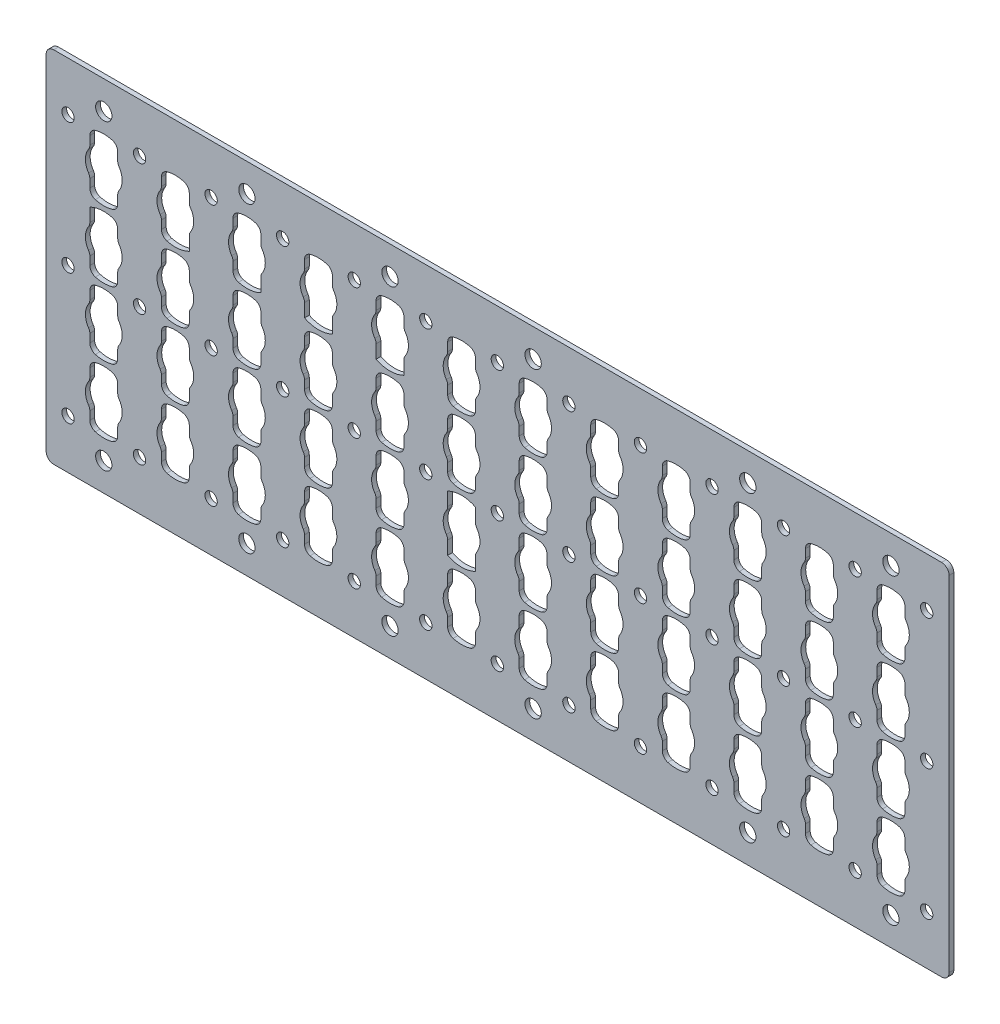
SolidWorks part; units mm, degrees
material "E-Glass Fiber"
ref_plane "X-Y Datum" through (0, 0, 0) normal (0, 0, 1) x (1, 0, 0)
ref_plane "X-Z Datum" through (0, 0, 0) normal (0, 1, 0) x (1, 0, 0)
ref_plane "Y-Z Datum" through (0, 0, 0) normal (1, 0, 0) x (0, 0, -1)
sketch "Sketch1" plane through (0, 0, 0) normal (0, 0, 1) x (1, 0, 0)
  line L1 (-10.2406, 8) -> (78.318, 8)
  line L2 (-10.2406, 8) -> (-10.2406, 16.1972)
  line L7 (-10.2406, 16.1972) -> (78.318, 16.1972)
  line L8 (78.318, 8) -> (78.318, 16.1972)
  line L12 (84.583, 16.1972) -> (87.883, 16.1972) construction
  line L17 (84.583, 4.7) -> (87.883, 4.7) construction
  line L20 (78.318, 0) -> (82.128, 0) construction
  circle A0 centre (0, 0) radius 10.5
  circle A24 centre (0, 0) radius 8 construction
  circle A25 centre (0, 0) radius 4.7 construction
  circle A46 centre (-3.5188, 13.3573) radius 2.5146 construction
  circle A47 centre (-3.5188, 13.3573) radius 1.1913 construction
  circle A78 centre (22.606, 0) radius 10.5
  circle A79 centre (22.606, 0) radius 8 construction
  circle A80 centre (22.606, 0) radius 4.7 construction
  circle A81 centre (45.212, 0) radius 10.5
  circle A82 centre (45.212, 0) radius 8 construction
  circle A83 centre (45.212, 0) radius 4.7 construction
  circle A84 centre (67.818, 0) radius 10.5
  circle A85 centre (67.818, 0) radius 8 construction
  circle A86 centre (67.818, 0) radius 4.7 construction
  circle A87 centre (0, 24.13) radius 10.5
  circle A88 centre (0, 24.13) radius 8 construction
  circle A89 centre (0, 24.13) radius 4.7 construction
  circle A90 centre (22.606, 24.13) radius 10.5
  circle A91 centre (22.606, 24.13) radius 8 construction
  circle A92 centre (22.606, 24.13) radius 4.7 construction
  circle A93 centre (45.212, 24.13) radius 10.5
  circle A94 centre (45.212, 24.13) radius 8 construction
  circle A95 centre (45.212, 24.13) radius 4.7 construction
  circle A96 centre (67.818, 24.13) radius 10.5
  circle A97 centre (67.818, 24.13) radius 8 construction
  circle A98 centre (67.818, 24.13) radius 4.7 construction
  circle A99 centre (0, 48.26) radius 10.5
  circle A100 centre (0, 48.26) radius 8 construction
  circle A101 centre (0, 48.26) radius 4.7 construction
  circle A102 centre (22.606, 48.26) radius 10.5
  circle A103 centre (22.606, 48.26) radius 8 construction
  circle A104 centre (22.606, 48.26) radius 4.7 construction
  circle A105 centre (45.212, 48.26) radius 10.5
  circle A106 centre (45.212, 48.26) radius 8 construction
  circle A107 centre (45.212, 48.26) radius 4.7 construction
  circle A108 centre (67.818, 48.26) radius 10.5
  circle A109 centre (67.818, 48.26) radius 8 construction
  circle A110 centre (67.818, 48.26) radius 4.7 construction
  circle A111 centre (0, 72.39) radius 10.5
  circle A112 centre (0, 72.39) radius 8 construction
  circle A113 centre (0, 72.39) radius 4.7 construction
  circle A114 centre (22.606, 72.39) radius 10.5
  circle A115 centre (22.606, 72.39) radius 8 construction
  circle A116 centre (22.606, 72.39) radius 4.7 construction
  circle A117 centre (45.212, 72.39) radius 10.5
  circle A118 centre (45.212, 72.39) radius 8 construction
  circle A119 centre (45.212, 72.39) radius 4.7 construction
  circle A120 centre (67.818, 72.39) radius 10.5
  circle A121 centre (67.818, 72.39) radius 8 construction
  circle A122 centre (67.818, 72.39) radius 4.7 construction
  circle A123 centre (0, 96.52) radius 10.5
  circle A124 centre (0, 96.52) radius 8 construction
  circle A125 centre (0, 96.52) radius 4.7 construction
  circle A126 centre (22.606, 96.52) radius 10.5
  circle A127 centre (22.606, 96.52) radius 8 construction
  circle A128 centre (22.606, 96.52) radius 4.7 construction
  circle A129 centre (45.212, 96.52) radius 10.5
  circle A130 centre (45.212, 96.52) radius 8 construction
  circle A131 centre (45.212, 96.52) radius 4.7 construction
  circle A132 centre (67.818, 96.52) radius 10.5
  circle A133 centre (67.818, 96.52) radius 8 construction
  circle A134 centre (67.818, 96.52) radius 4.7 construction
  circle A135 centre (0, 120.65) radius 10.5
  circle A136 centre (0, 120.65) radius 8 construction
  circle A137 centre (0, 120.65) radius 4.7 construction
  circle A138 centre (22.606, 120.65) radius 10.5
  circle A139 centre (22.606, 120.65) radius 8 construction
  circle A140 centre (22.606, 120.65) radius 4.7 construction
  circle A141 centre (45.212, 120.65) radius 10.5
  circle A142 centre (45.212, 120.65) radius 8 construction
  circle A143 centre (45.212, 120.65) radius 4.7 construction
  circle A144 centre (67.818, 120.65) radius 10.5
  circle A145 centre (67.818, 120.65) radius 8 construction
  circle A146 centre (67.818, 120.65) radius 4.7 construction
  dimension "D1" = 4
  dimension "D9" = 9.4
  dimension "D4" = 2.5
  dimension "D2" = 6
sketch "Sketch2" plane through (0, 0, 0) normal (0, 0, 1) x (1, 0, 0)
  line L0 (28.8471, 78.318) -> (28.8471, -10.5) construction
  line L5 (4.7, 78.318) -> (19.43, 78.318) construction
  line L6 (4.7, 78.318) -> (4.7, -10.5) construction
  line L7 (4.7, -10.5) -> (19.43, -10.5) construction
  line L8 (19.43, 78.318) -> (19.43, -10.5) construction
  line L9 (28.8471, 78.318) -> (43.5771, 78.318) construction
  line L10 (43.5771, 78.318) -> (43.5771, -10.5) construction
  line L11 (28.8471, -10.5) -> (43.5771, -10.5) construction
  line L12 (52.9942, 78.318) -> (52.9942, -10.5) construction
  line L13 (52.9942, 78.318) -> (67.7242, 78.318) construction
  line L14 (67.7242, 78.318) -> (67.7242, -10.5) construction
  line L15 (52.9942, -10.5) -> (67.7242, -10.5) construction
  line L16 (77.1413, 78.318) -> (77.1413, -10.5) construction
  line L17 (77.1413, 78.318) -> (91.8713, 78.318) construction
  line L18 (91.8713, 78.318) -> (91.8713, -10.5) construction
  line L19 (77.1413, -10.5) -> (91.8713, -10.5) construction
  line L20 (101.2884, 78.318) -> (101.2884, -10.5) construction
  line L21 (101.2884, 78.318) -> (116.0184, 78.318) construction
  line L22 (116.0184, 78.318) -> (116.0184, -10.5) construction
  line L23 (101.2884, -10.5) -> (116.0184, -10.5) construction
  line L24 (125.4355, 78.318) -> (125.4355, -10.5) construction
  line L25 (125.4355, 78.318) -> (140.1655, 78.318) construction
  line L26 (140.1655, 78.318) -> (140.1655, -10.5) construction
  line L27 (125.4355, -10.5) -> (140.1655, -10.5) construction
  line L28 (149.5826, 78.318) -> (149.5826, -10.5) construction
  line L29 (149.5826, 78.318) -> (164.3126, 78.318) construction
  line L30 (164.3126, 78.318) -> (164.3126, -10.5) construction
  line L31 (149.5826, -10.5) -> (164.3126, -10.5) construction
  line L32 (173.7297, 78.318) -> (173.7297, -10.5) construction
  line L33 (173.7297, 78.318) -> (188.4597, 78.318) construction
  line L34 (188.4597, 78.318) -> (188.4597, -10.5) construction
  line L35 (173.7297, -10.5) -> (188.4597, -10.5) construction
  line L36 (197.8768, 78.318) -> (197.8768, -10.5) construction
  line L37 (197.8768, 78.318) -> (212.6068, 78.318) construction
  line L38 (212.6068, 78.318) -> (212.6068, -10.5) construction
  line L39 (197.8768, -10.5) -> (212.6068, -10.5) construction
  line L40 (222.0239, 78.318) -> (222.0239, -10.5) construction
  line L41 (222.0239, 78.318) -> (236.7539, 78.318) construction
  line L42 (236.7539, 78.318) -> (236.7539, -10.5) construction
  line L43 (222.0239, -10.5) -> (236.7539, -10.5) construction
  line L44 (246.171, 78.318) -> (246.171, -10.5) construction
  line L45 (246.171, 78.318) -> (260.901, 78.318) construction
  line L46 (260.901, 78.318) -> (260.901, -10.5) construction
  line L47 (246.171, -10.5) -> (260.901, -10.5) construction
  line L48 (270.3181, 78.318) -> (270.3181, -10.5) construction
  line L49 (270.3181, 78.318) -> (285.0481, 78.318) construction
  line L50 (285.0481, 78.318) -> (285.0481, -10.5) construction
  line L51 (270.3181, -10.5) -> (285.0481, -10.5) construction
  line L52 (-19.43, 78.318) -> (-19.43, -10.5) construction
  line L53 (-19.43, 78.318) -> (-4.7, 78.318) construction
  line L54 (-4.7, 78.318) -> (-4.7, -10.5) construction
  line L55 (-19.43, -10.5) -> (-4.7, -10.5) construction
  line L56 (0, 78.3179) -> (0, 91.526) construction
  line L57 (0, -10.4999) -> (0, -23.708) construction
  line L58 (-27.6439, 33.909) -> (301.0934, 33.909) construction
  line L59 (-19.43, 91.526) -> (285.0481, 91.526) construction
  line L60 (-19.43, 91.526) -> (-19.43, -23.708)
  line L61 (-19.43, -23.708) -> (285.0481, -23.708) construction
  line L62 (285.0481, 91.526) -> (285.0481, -23.708)
  line L63 (-19.43, 91.526) -> (-19.43, 94.447)
  line L64 (-19.43, 94.447) -> (285.0481, 94.447)
  line L65 (285.0481, 94.447) -> (285.0481, 91.526)
  line L66 (-19.43, -23.708) -> (-19.43, -26.629)
  line L67 (-19.43, -26.629) -> (285.0481, -26.629)
  line L68 (285.0481, -26.629) -> (285.0481, -23.708)
  circle A0 centre (0, 0) radius 10.4999
  circle A8 centre (0, 0) radius 4.7 construction
  circle A10 centre (24.13, 0) radius 10.4999
  circle A11 centre (48.26, 0) radius 10.4999
  circle A12 centre (72.39, 0) radius 10.4999
  circle A13 centre (24.13, 22.606) radius 10.4999
  circle A14 centre (48.26, 22.606) radius 10.4999
  circle A15 centre (72.39, 22.606) radius 10.4999
  circle A16 centre (24.13, 45.212) radius 10.4999
  circle A17 centre (48.26, 45.212) radius 10.4999
  circle A18 centre (72.39, 45.212) radius 10.4999
  circle A19 centre (24.13, 67.818) radius 10.4999
  circle A20 centre (48.26, 67.818) radius 10.4999
  circle A21 centre (72.39, 67.818) radius 10.4999
  circle A28 centre (0, 22.606) radius 10.4999
  circle A29 centre (0, 45.212) radius 10.4999
  circle A30 centre (0, 67.818) radius 10.4999
  circle A33 centre (0, 0) radius 8 construction
  circle A34 centre (96.52, 0) radius 10.4999
  circle A35 centre (120.65, 0) radius 10.4999
  circle A36 centre (144.78, 0) radius 10.4999
  circle A37 centre (168.91, 0) radius 10.4999
  circle A38 centre (193.04, 0) radius 10.4999
  circle A39 centre (217.17, 0) radius 10.4999
  circle A40 centre (241.3, 0) radius 10.4999
  circle A41 centre (265.43, 0) radius 10.4999
  circle A42 centre (96.52, 22.606) radius 10.4999
  circle A43 centre (120.65, 22.606) radius 10.4999
  circle A44 centre (144.78, 22.606) radius 10.4999
  circle A45 centre (168.91, 22.606) radius 10.4999
  circle A46 centre (193.04, 22.606) radius 10.4999
  circle A47 centre (217.17, 22.606) radius 10.4999
  circle A48 centre (241.3, 22.606) radius 10.4999
  circle A49 centre (265.43, 22.606) radius 10.4999
  circle A50 centre (96.52, 45.212) radius 10.4999
  circle A51 centre (120.65, 45.212) radius 10.4999
  circle A52 centre (144.78, 45.212) radius 10.4999
  circle A53 centre (168.91, 45.212) radius 10.4999
  circle A54 centre (193.04, 45.212) radius 10.4999
  circle A55 centre (217.17, 45.212) radius 10.4999
  circle A56 centre (241.3, 45.212) radius 10.4999
  circle A57 centre (265.43, 45.212) radius 10.4999
  circle A58 centre (96.52, 67.818) radius 10.4999
  circle A59 centre (120.65, 67.818) radius 10.4999
  circle A60 centre (144.78, 67.818) radius 10.4999
  circle A61 centre (168.91, 67.818) radius 10.4999
  circle A62 centre (193.04, 67.818) radius 10.4999
  circle A63 centre (217.17, 67.818) radius 10.4999
  circle A64 centre (241.3, 67.818) radius 10.4999
  circle A65 centre (265.43, 67.818) radius 10.4999
  circle A82 centre (24.13, 0) radius 8 construction
  circle A83 centre (24.13, 0) radius 4.7 construction
  circle A84 centre (48.26, 0) radius 8 construction
  circle A85 centre (48.26, 0) radius 4.7 construction
  circle A86 centre (72.39, 0) radius 8 construction
  circle A87 centre (72.39, 0) radius 4.7 construction
  circle A88 centre (96.52, 0) radius 8 construction
  circle A89 centre (96.52, 0) radius 4.7 construction
  circle A90 centre (120.65, 0) radius 8 construction
  circle A91 centre (120.65, 0) radius 4.7 construction
  circle A92 centre (144.78, 0) radius 8 construction
  circle A93 centre (144.78, 0) radius 4.7 construction
  circle A94 centre (168.91, 0) radius 8 construction
  circle A95 centre (168.91, 0) radius 4.7 construction
  circle A96 centre (193.04, 0) radius 8 construction
  circle A97 centre (193.04, 0) radius 4.7 construction
  circle A98 centre (217.17, 0) radius 8 construction
  circle A99 centre (217.17, 0) radius 4.7 construction
  circle A100 centre (241.3, 0) radius 8 construction
  circle A101 centre (241.3, 0) radius 4.7 construction
  circle A102 centre (265.43, 0) radius 8 construction
  circle A103 centre (265.43, 0) radius 4.7 construction
  circle A104 centre (24.13, 22.606) radius 8 construction
  circle A105 centre (24.13, 22.606) radius 4.7 construction
  circle A106 centre (48.26, 22.606) radius 8 construction
  circle A107 centre (48.26, 22.606) radius 4.7 construction
  circle A108 centre (72.39, 22.606) radius 8 construction
  circle A109 centre (72.39, 22.606) radius 4.7 construction
  circle A110 centre (96.52, 22.606) radius 8 construction
  circle A111 centre (96.52, 22.606) radius 4.7 construction
  circle A112 centre (120.65, 22.606) radius 8 construction
  circle A113 centre (120.65, 22.606) radius 4.7 construction
  circle A114 centre (144.78, 22.606) radius 8 construction
  circle A115 centre (144.78, 22.606) radius 4.7 construction
  circle A116 centre (168.91, 22.606) radius 8 construction
  circle A117 centre (168.91, 22.606) radius 4.7 construction
  circle A118 centre (193.04, 22.606) radius 8 construction
  circle A119 centre (193.04, 22.606) radius 4.7 construction
  circle A120 centre (217.17, 22.606) radius 8 construction
  circle A121 centre (217.17, 22.606) radius 4.7 construction
  circle A122 centre (241.3, 22.606) radius 8 construction
  circle A123 centre (241.3, 22.606) radius 4.7 construction
  circle A124 centre (265.43, 22.606) radius 8 construction
  circle A125 centre (265.43, 22.606) radius 4.7 construction
  circle A126 centre (24.13, 45.212) radius 8 construction
  circle A127 centre (24.13, 45.212) radius 4.7 construction
  circle A128 centre (48.26, 45.212) radius 8 construction
  circle A129 centre (48.26, 45.212) radius 4.7 construction
  circle A130 centre (72.39, 45.212) radius 8 construction
  circle A131 centre (72.39, 45.212) radius 4.7 construction
  circle A132 centre (96.52, 45.212) radius 8 construction
  circle A133 centre (96.52, 45.212) radius 4.7 construction
  circle A134 centre (120.65, 45.212) radius 8 construction
  circle A135 centre (120.65, 45.212) radius 4.7 construction
  circle A136 centre (144.78, 45.212) radius 8 construction
  circle A137 centre (144.78, 45.212) radius 4.7 construction
  circle A138 centre (168.91, 45.212) radius 8 construction
  circle A139 centre (168.91, 45.212) radius 4.7 construction
  circle A140 centre (193.04, 45.212) radius 8 construction
  circle A141 centre (193.04, 45.212) radius 4.7 construction
  circle A142 centre (217.17, 45.212) radius 8 construction
  circle A143 centre (217.17, 45.212) radius 4.7 construction
  circle A144 centre (241.3, 45.212) radius 8 construction
  circle A145 centre (241.3, 45.212) radius 4.7 construction
  circle A146 centre (265.43, 45.212) radius 8 construction
  circle A147 centre (265.43, 45.212) radius 4.7 construction
  circle A148 centre (24.13, 67.818) radius 8 construction
  circle A149 centre (24.13, 67.818) radius 4.7 construction
  circle A150 centre (48.26, 67.818) radius 8 construction
  circle A151 centre (48.26, 67.818) radius 4.7 construction
  circle A152 centre (72.39, 67.818) radius 8 construction
  circle A153 centre (72.39, 67.818) radius 4.7 construction
  circle A154 centre (96.52, 67.818) radius 8 construction
  circle A155 centre (96.52, 67.818) radius 4.7 construction
  circle A156 centre (120.65, 67.818) radius 8 construction
  circle A157 centre (120.65, 67.818) radius 4.7 construction
  circle A158 centre (144.78, 67.818) radius 8 construction
  circle A159 centre (144.78, 67.818) radius 4.7 construction
  circle A160 centre (168.91, 67.818) radius 8 construction
  circle A161 centre (168.91, 67.818) radius 4.7 construction
  circle A162 centre (193.04, 67.818) radius 8 construction
  circle A163 centre (193.04, 67.818) radius 4.7 construction
  circle A164 centre (217.17, 67.818) radius 8 construction
  circle A165 centre (217.17, 67.818) radius 4.7 construction
  circle A166 centre (241.3, 67.818) radius 8 construction
  circle A167 centre (241.3, 67.818) radius 4.7 construction
  circle A168 centre (265.43, 67.818) radius 8 construction
  circle A169 centre (265.43, 67.818) radius 4.7 construction
  circle A170 centre (0, 22.606) radius 8 construction
  circle A171 centre (0, 22.606) radius 4.7 construction
  circle A172 centre (0, 45.212) radius 8 construction
  circle A173 centre (0, 45.212) radius 4.7 construction
  circle A174 centre (0, 67.818) radius 8 construction
  circle A175 centre (0, 67.818) radius 4.7 construction
  circle A178 centre (0, 84.922) radius 2.752
  circle A181 centre (48.26, 84.922) radius 2.752
  circle A183 centre (96.52, 84.922) radius 2.752
  circle A185 centre (144.78, 84.922) radius 2.752
  circle A188 centre (217.17, 84.922) radius 2.752
  circle A190 centre (265.43, 84.922) radius 2.752
  circle A191 centre (24.13, 84.922) radius 2.752 [skipped]
  circle A192 centre (72.39, 84.922) radius 2.752 [skipped]
  circle A193 centre (120.65, 84.922) radius 2.752 [skipped]
  circle A194 centre (193.04, 84.922) radius 2.752 [skipped]
  circle A195 centre (241.3, 84.922) radius 2.752 [skipped]
  circle A196 centre (168.91, 84.922) radius 2.752 [skipped]
  circle A197 centre (265.43, -17.104) radius 2.752
  circle A198 centre (217.17, -17.104) radius 2.752
  circle A199 centre (144.78, -17.104) radius 2.752
  circle A200 centre (96.52, -17.104) radius 2.752
  circle A201 centre (48.26, -17.104) radius 2.752
  circle A202 centre (0, -17.104) radius 2.752
  dimension "D1" = 12
  dimension "D3" = 12
  dimension "D5" = 12
  dimension "D2" = 4
  dimension "D4" = 2
extrude "Boss-Extrude1" add sketch "Sketch2" along normal blind 1.6
sketch "Sketch3" plane through (0, 0, 1.6) normal (0, 0, 1) x (1, 0, 0)
  line L0 (10.4999, 67.818) -> (13.6301, 67.818) construction
  line L1 (4.7, 78.318) -> (19.43, 78.318) construction
  line L2 (4.7, 78.318) -> (4.7, -10.5) construction
  line L3 (4.7, -10.5) -> (19.43, -10.5) construction
  line L4 (19.43, 78.318) -> (19.43, -10.5) construction
  line L5 (12.065, 67.818) -> (12.065, 78.318) construction
  line L6 (4.7, 33.909) -> (19.43, 33.909) construction
  line L7 (12.065, 78.318) -> (12.065, -10.5) construction
  line L8 (10.4999, 0) -> (13.6301, 0) construction
  circle A0 centre (0, 0) radius 4.7 construction
  circle A1 centre (0, 0) radius 6.2 construction
  circle A2 centre (0, 67.818) radius 10.4999 construction
  circle A3 centre (24.13, 67.818) radius 10.4999 construction
  circle A4 centre (12.065, 77.8952) radius 2.5146 construction
  circle A5 centre (12.065, 77.8952) radius 2.0828
  circle A6 centre (12.065, -10.0772) radius 2.0828
  circle A7 centre (12.065, -10.0772) radius 2.5146 construction
  circle A32 centre (36.195, 77.8952) radius 2.0828
  circle A33 centre (60.325, 77.8952) radius 2.0828
  circle A34 centre (84.455, 77.8952) radius 2.0828
  circle A35 centre (108.585, 77.8952) radius 2.0828
  circle A36 centre (132.715, 77.8952) radius 2.0828
  circle A37 centre (156.845, 77.8952) radius 2.0828
  circle A38 centre (180.975, 77.8952) radius 2.0828
  circle A39 centre (205.105, 77.8952) radius 2.0828
  circle A40 centre (229.235, 77.8952) radius 2.0828
  circle A41 centre (253.365, 77.8952) radius 2.0828
  circle A42 centre (277.495, 77.8952) radius 2.0828
  circle A43 centre (-12.065, 77.8952) radius 2.0828
  circle A44 centre (277.495, -10.0772) radius 2.0828
  circle A45 centre (253.365, -10.0772) radius 2.0828
  circle A46 centre (229.235, -10.0772) radius 2.0828
  circle A47 centre (205.105, -10.0772) radius 2.0828
  circle A48 centre (180.975, -10.0772) radius 2.0828
  circle A49 centre (156.845, -10.0772) radius 2.0828
  circle A50 centre (132.715, -10.0772) radius 2.0828
  circle A51 centre (108.585, -10.0772) radius 2.0828
  circle A52 centre (84.455, -10.0772) radius 2.0828
  circle A53 centre (60.325, -10.0772) radius 2.0828
  circle A54 centre (36.195, -10.0772) radius 2.0828
  circle A55 centre (-12.065, -10.0772) radius 2.0828
  circle A56 centre (12.065, 33.909) radius 2.0828
  circle A57 centre (36.195, 33.909) radius 2.0828
  circle A58 centre (60.325, 33.909) radius 2.0828
  circle A59 centre (84.455, 33.909) radius 2.0828
  circle A60 centre (108.585, 33.909) radius 2.0828
  circle A61 centre (132.715, 33.909) radius 2.0828
  circle A62 centre (156.845, 33.909) radius 2.0828
  circle A63 centre (180.975, 33.909) radius 2.0828
  circle A64 centre (205.105, 33.909) radius 2.0828
  circle A65 centre (229.235, 33.909) radius 2.0828
  circle A66 centre (253.365, 33.909) radius 2.0828
  circle A67 centre (277.495, 33.909) radius 2.0828
  circle A68 centre (-12.065, 33.909) radius 2.0828
  circle A69 centre (0, 0) radius 10.4999 construction
  circle A70 centre (24.13, 0) radius 10.4999 construction
  point P109 (0, 0)
  dimension "D2" = 12
  dimension "D4" = 10.0772
  dimension "D5" = 4.1656
  dimension "D6" = 10.0772
  dimension "D1" = 1.5
  dimension "D3" = 2
sketch "Sketch5" plane through (0, 0, 1.6) normal (0, 0, 1) x (1, 0, 0)
  line L1 (-19.43, 94.447) -> (-22.605, 94.447)
  line L2 (-19.43, 94.447) -> (-19.43, -26.629)
  line L3 (-19.43, -26.629) -> (-22.605, -26.629)
  line L4 (-22.605, 94.447) -> (-22.605, -26.629)
  line L5 (285.0481, 94.447) -> (288.2231, 94.447)
  line L6 (285.0481, 94.447) -> (285.0481, -26.629)
  line L7 (285.0481, -26.629) -> (288.2231, -26.629)
  line L8 (288.2231, 94.447) -> (288.2231, -26.629)
extrude "Boss-Extrude2" [suppressed] add sketch "Sketch5" against normal through all
sketch "Sketch7" plane through (0, 0, 1.6) normal (0, 0, 1) x (1, 0, 0)
  line L156 (19.43, 62.9223) -> (19.43, 50.1077)
  line L157 (4.7, 78.318) -> (19.43, 78.318)
  line L158 (4.7, 78.318) -> (4.7, 72.7137)
  line L159 (4.7, -10.5) -> (19.43, -10.5)
  line L160 (19.43, 78.318) -> (19.43, 72.7137)
  line L161 (19.43, 40.3163) -> (19.43, 27.5017)
  line L162 (19.43, 17.7103) -> (19.43, 4.8957)
  line L163 (19.43, -4.8957) -> (19.43, -10.5)
  line L164 (4.7, -4.8957) -> (4.7, -10.5)
  line L165 (4.7, 17.7103) -> (4.7, 4.8957)
  line L166 (4.7, 40.3163) -> (4.7, 27.5017)
  line L167 (4.7, 62.9223) -> (4.7, 50.1077)
  line L456 (28.83, 17.7103) -> (28.83, 4.8957)
  line L457 (28.83, 40.3163) -> (28.83, 27.5017)
  line L458 (28.83, 62.9223) -> (28.83, 50.1077)
  line L459 (28.83, 78.318) -> (28.83, 72.7137)
  line L460 (28.83, 78.318) -> (43.56, 78.318)
  line L461 (43.56, 78.318) -> (43.56, 72.7137)
  line L462 (43.56, 62.9223) -> (43.56, 50.1077)
  line L463 (43.56, 40.3163) -> (43.56, 27.5017)
  line L464 (43.56, 17.7103) -> (43.56, 4.8957)
  line L465 (43.56, -4.8957) -> (43.56, -10.5)
  line L466 (28.83, -10.5) -> (43.56, -10.5)
  line L467 (28.83, -4.8957) -> (28.83, -10.5)
  line L468 (52.96, 17.7103) -> (52.96, 4.8957)
  line L469 (52.96, 40.3163) -> (52.96, 27.5017)
  line L470 (52.96, 62.9223) -> (52.96, 50.1077)
  line L471 (52.96, 78.318) -> (52.96, 72.7137)
  line L472 (52.96, 78.318) -> (67.69, 78.318)
  line L473 (67.69, 78.318) -> (67.69, 72.7137)
  line L474 (67.69, 62.9223) -> (67.69, 50.1077)
  line L475 (67.69, 40.3163) -> (67.69, 27.5017)
  line L476 (67.69, 17.7103) -> (67.69, 4.8957)
  line L477 (67.69, -4.8957) -> (67.69, -10.5)
  line L478 (52.96, -10.5) -> (67.69, -10.5)
  line L479 (52.96, -4.8957) -> (52.96, -10.5)
  line L480 (77.09, 17.7103) -> (77.09, 4.8957)
  line L481 (77.09, 40.3163) -> (77.09, 27.5017)
  line L482 (77.09, 62.9223) -> (77.09, 50.1077)
  line L483 (77.09, 78.318) -> (77.09, 72.7137)
  line L484 (77.09, 78.318) -> (91.82, 78.318)
  line L485 (91.82, 78.318) -> (91.82, 72.7137)
  line L486 (91.82, 62.9223) -> (91.82, 50.1077)
  line L487 (91.82, 40.3163) -> (91.82, 27.5017)
  line L488 (91.82, 17.7103) -> (91.82, 4.8957)
  line L489 (91.82, -4.8957) -> (91.82, -10.5)
  line L490 (77.09, -10.5) -> (91.82, -10.5)
  line L491 (77.09, -4.8957) -> (77.09, -10.5)
  line L492 (101.22, 17.7103) -> (101.22, 4.8957)
  line L493 (101.22, 40.3163) -> (101.22, 27.5017)
  line L494 (101.22, 62.9223) -> (101.22, 50.1077)
  line L495 (101.22, 78.318) -> (101.22, 72.7137)
  line L496 (101.22, 78.318) -> (115.95, 78.318)
  line L497 (115.95, 78.318) -> (115.95, 72.7137)
  line L498 (115.95, 62.9223) -> (115.95, 50.1077)
  line L499 (115.95, 40.3163) -> (115.95, 27.5017)
  line L500 (115.95, 17.7103) -> (115.95, 4.8957)
  line L501 (115.95, -4.8957) -> (115.95, -10.5)
  line L502 (101.22, -10.5) -> (115.95, -10.5)
  line L503 (101.22, -4.8957) -> (101.22, -10.5)
  line L504 (125.35, 17.7103) -> (125.35, 4.8957)
  line L505 (125.35, 40.3163) -> (125.35, 27.5017)
  line L506 (125.35, 62.9223) -> (125.35, 50.1077)
  line L507 (125.35, 78.318) -> (125.35, 72.7137)
  line L508 (125.35, 78.318) -> (140.08, 78.318)
  line L509 (140.08, 78.318) -> (140.08, 72.7137)
  line L510 (140.08, 62.9223) -> (140.08, 50.1077)
  line L511 (140.08, 40.3163) -> (140.08, 27.5017)
  line L512 (140.08, 17.7103) -> (140.08, 4.8957)
  line L513 (140.08, -4.8957) -> (140.08, -10.5)
  line L514 (125.35, -10.5) -> (140.08, -10.5)
  line L515 (125.35, -4.8957) -> (125.35, -10.5)
  line L516 (149.48, 17.7103) -> (149.48, 4.8957)
  line L517 (149.48, 40.3163) -> (149.48, 27.5017)
  line L518 (149.48, 62.9223) -> (149.48, 50.1077)
  line L519 (149.48, 78.318) -> (149.48, 72.7137)
  line L520 (149.48, 78.318) -> (164.21, 78.318)
  line L521 (164.21, 78.318) -> (164.21, 72.7137)
  line L522 (164.21, 62.9223) -> (164.21, 50.1077)
  line L523 (164.21, 40.3163) -> (164.21, 27.5017)
  line L524 (164.21, 17.7103) -> (164.21, 4.8957)
  line L525 (164.21, -4.8957) -> (164.21, -10.5)
  line L526 (149.48, -10.5) -> (164.21, -10.5)
  line L527 (149.48, -4.8957) -> (149.48, -10.5)
  line L528 (173.61, 17.7103) -> (173.61, 4.8957)
  line L529 (173.61, 40.3163) -> (173.61, 27.5017)
  line L530 (173.61, 62.9223) -> (173.61, 50.1077)
  line L531 (173.61, 78.318) -> (173.61, 72.7137)
  line L532 (173.61, 78.318) -> (188.34, 78.318)
  line L533 (188.34, 78.318) -> (188.34, 72.7137)
  line L534 (188.34, 62.9223) -> (188.34, 50.1077)
  line L535 (188.34, 40.3163) -> (188.34, 27.5017)
  line L536 (188.34, 17.7103) -> (188.34, 4.8957)
  line L537 (188.34, -4.8957) -> (188.34, -10.5)
  line L538 (173.61, -10.5) -> (188.34, -10.5)
  line L539 (173.61, -4.8957) -> (173.61, -10.5)
  line L540 (197.74, 17.7103) -> (197.74, 4.8957)
  line L541 (197.74, 40.3163) -> (197.74, 27.5017)
  line L542 (197.74, 62.9223) -> (197.74, 50.1077)
  line L543 (197.74, 78.318) -> (197.74, 72.7137)
  line L544 (197.74, 78.318) -> (212.47, 78.318)
  line L545 (212.47, 78.318) -> (212.47, 72.7137)
  line L546 (212.47, 62.9223) -> (212.47, 50.1077)
  line L547 (212.47, 40.3163) -> (212.47, 27.5017)
  line L548 (212.47, 17.7103) -> (212.47, 4.8957)
  line L549 (212.47, -4.8957) -> (212.47, -10.5)
  line L550 (197.74, -10.5) -> (212.47, -10.5)
  line L551 (197.74, -4.8957) -> (197.74, -10.5)
  line L552 (221.87, 17.7103) -> (221.87, 4.8957)
  line L553 (221.87, 40.3163) -> (221.87, 27.5017)
  line L554 (221.87, 62.9223) -> (221.87, 50.1077)
  line L555 (221.87, 78.318) -> (221.87, 72.7137)
  line L556 (221.87, 78.318) -> (236.6, 78.318)
  line L557 (236.6, 78.318) -> (236.6, 72.7137)
  line L558 (236.6, 62.9223) -> (236.6, 50.1077)
  line L559 (236.6, 40.3163) -> (236.6, 27.5017)
  line L560 (236.6, 17.7103) -> (236.6, 4.8957)
  line L561 (236.6, -4.8957) -> (236.6, -10.5)
  line L562 (221.87, -10.5) -> (236.6, -10.5)
  line L563 (221.87, -4.8957) -> (221.87, -10.5)
  line L564 (246, 17.7103) -> (246, 4.8957)
  line L565 (246, 40.3163) -> (246, 27.5017)
  line L566 (246, 62.9223) -> (246, 50.1077)
  line L567 (246, 78.318) -> (246, 72.7137)
  line L568 (246, 78.318) -> (260.73, 78.318)
  line L569 (260.73, 78.318) -> (260.73, 72.7137)
  line L570 (260.73, 62.9223) -> (260.73, 50.1077)
  line L571 (260.73, 40.3163) -> (260.73, 27.5017)
  line L572 (260.73, 17.7103) -> (260.73, 4.8957)
  line L573 (260.73, -4.8957) -> (260.73, -10.5)
  line L574 (246, -10.5) -> (260.73, -10.5)
  line L575 (246, -4.8957) -> (246, -10.5)
  line L576 (270.13, 17.7103) -> (270.13, 4.8957)
  line L577 (270.13, 40.3163) -> (270.13, 27.5017)
  line L578 (270.13, 62.9223) -> (270.13, 50.1077)
  line L579 (270.13, 78.318) -> (270.13, 72.7137)
  line L580 (270.13, 78.318) -> (284.86, 78.318)
  line L581 (284.86, 78.318) -> (284.86, 72.7137)
  line L582 (284.86, 62.9223) -> (284.86, 50.1077)
  line L583 (284.86, 40.3163) -> (284.86, 27.5017)
  line L584 (284.86, 17.7103) -> (284.86, 4.8957)
  line L585 (284.86, -4.8957) -> (284.86, -10.5)
  line L586 (270.13, -10.5) -> (284.86, -10.5)
  line L587 (270.13, -4.8957) -> (270.13, -10.5)
  line L588 (-19.43, 17.7103) -> (-19.43, 4.8957)
  line L589 (-19.43, 40.3163) -> (-19.43, 27.5017)
  line L590 (-19.43, 62.9223) -> (-19.43, 50.1077)
  line L591 (-19.43, 78.318) -> (-19.43, 72.7137)
  line L592 (-19.43, 78.318) -> (-4.7, 78.318)
  line L593 (-4.7, 78.318) -> (-4.7, 72.7137)
  line L594 (-4.7, 62.9223) -> (-4.7, 50.1077)
  line L595 (-4.7, 40.3163) -> (-4.7, 27.5017)
  line L596 (-4.7, 17.7103) -> (-4.7, 4.8957)
  line L597 (-4.7, -4.8957) -> (-4.7, -10.5)
  line L598 (-19.43, -10.5) -> (-4.7, -10.5)
  line L599 (-19.43, -4.8957) -> (-19.43, -10.5)
  circle A130 centre (12.065, 75.3552) radius 1.2319
  circle A131 centre (12.065, -7.5372) radius 1.2319
  arc A132 (5.1359, -3.4729) -> (4.7, -4.8957) centre (7.24, -4.8957) ccw
  arc A133 (5.1359, 3.4729) -> (4.7, 4.8957) centre (7.24, 4.8957) cw
  circle A134 centre (0, 0) radius 6.1999
  arc A135 (5.1359, -3.4729) -> (5.1359, 3.4729) centre (0, 0) ccw
  arc A136 (18.9941, 3.4729) -> (19.43, 4.8957) centre (16.89, 4.8957) ccw
  circle A137 centre (24.13, 0) radius 6.1999
  arc A138 (18.9941, 3.4729) -> (18.9941, -3.4729) centre (24.13, 0) ccw
  arc A139 (18.9941, -3.4729) -> (19.43, -4.8957) centre (16.89, -4.8957) cw
  circle A140 centre (24.13, 22.606) radius 6.1999
  arc A141 (18.9941, 26.0789) -> (18.9941, 19.1331) centre (24.13, 22.606) ccw
  arc A142 (18.9941, 19.1331) -> (19.43, 17.7103) centre (16.89, 17.7103) cw
  circle A143 centre (0, 22.606) radius 6.1999
  arc A144 (5.1359, 19.1331) -> (5.1359, 26.0789) centre (0, 22.606) ccw
  arc A145 (5.1359, 19.1331) -> (4.7, 17.7103) centre (7.24, 17.7103) ccw
  circle A146 centre (0, 45.212) radius 6.1999
  arc A147 (5.1359, 41.7391) -> (5.1359, 48.6849) centre (0, 45.212) ccw
  arc A148 (5.1359, 41.7391) -> (4.7, 40.3163) centre (7.24, 40.3163) ccw
  circle A149 centre (24.13, 45.212) radius 6.1999
  arc A150 (18.9941, 48.6849) -> (18.9941, 41.7391) centre (24.13, 45.212) ccw
  arc A151 (18.9941, 41.7391) -> (19.43, 40.3163) centre (16.89, 40.3163) cw
  circle A152 centre (0, 67.818) radius 6.1999
  arc A153 (5.1359, 64.3451) -> (5.1359, 71.2909) centre (0, 67.818) ccw
  circle A155 centre (24.13, 67.818) radius 6.1999
  arc A156 (18.9941, 71.2909) -> (18.9941, 64.3451) centre (24.13, 67.818) ccw
  arc A276 (18.9941, 48.6849) -> (19.43, 50.1077) centre (16.89, 50.1077) ccw
  arc A277 (5.1359, 48.6849) -> (4.7, 50.1077) centre (7.24, 50.1077) cw
  arc A278 (18.9941, 71.2909) -> (19.43, 72.7137) centre (16.89, 72.7137) ccw
  arc A279 (18.9941, 64.3451) -> (19.43, 62.9223) centre (16.89, 62.9223) cw
  arc A280 (5.1359, 64.3451) -> (4.7, 62.9223) centre (7.24, 62.9223) ccw
  arc A281 (5.1359, 71.2909) -> (4.7, 72.7137) centre (7.24, 72.7137) cw
  arc A546 (18.9941, 26.0789) -> (19.43, 27.5017) centre (16.89, 27.5017) ccw
  arc A547 (5.1359, 26.0789) -> (4.7, 27.5017) centre (7.24, 27.5017) cw
  arc A548 (29.2659, -3.4729) -> (29.2659, 3.4729) centre (24.13, 0) ccw
  arc A549 (29.2659, 3.4729) -> (28.83, 4.8957) centre (31.37, 4.8957) cw
  arc A550 (29.2659, -3.4729) -> (28.83, -4.8957) centre (31.37, -4.8957) ccw
  arc A551 (29.2659, 19.1331) -> (28.83, 17.7103) centre (31.37, 17.7103) ccw
  arc A552 (29.2659, 19.1331) -> (29.2659, 26.0789) centre (24.13, 22.606) ccw
  arc A553 (29.2659, 26.0789) -> (28.83, 27.5017) centre (31.37, 27.5017) cw
  arc A554 (29.2659, 41.7391) -> (28.83, 40.3163) centre (31.37, 40.3163) ccw
  arc A555 (29.2659, 41.7391) -> (29.2659, 48.6849) centre (24.13, 45.212) ccw
  arc A556 (29.2659, 48.6849) -> (28.83, 50.1077) centre (31.37, 50.1077) cw
  arc A557 (29.2659, 64.3451) -> (28.83, 62.9223) centre (31.37, 62.9223) ccw
  arc A558 (29.2659, 64.3451) -> (29.2659, 71.2909) centre (24.13, 67.818) ccw
  arc A559 (29.2659, 71.2909) -> (28.83, 72.7137) centre (31.37, 72.7137) cw
  arc A560 (43.1241, 71.2909) -> (43.56, 72.7137) centre (41.02, 72.7137) ccw
  arc A561 (43.1241, 71.2909) -> (43.1241, 64.3451) centre (48.26, 67.818) ccw
  arc A562 (43.1241, 64.3451) -> (43.56, 62.9223) centre (41.02, 62.9223) cw
  arc A563 (43.1241, 48.6849) -> (43.56, 50.1077) centre (41.02, 50.1077) ccw
  arc A564 (43.1241, 48.6849) -> (43.1241, 41.7391) centre (48.26, 45.212) ccw
  arc A565 (43.1241, 41.7391) -> (43.56, 40.3163) centre (41.02, 40.3163) cw
  arc A566 (43.1241, 26.0789) -> (43.56, 27.5017) centre (41.02, 27.5017) ccw
  arc A567 (43.1241, 26.0789) -> (43.1241, 19.1331) centre (48.26, 22.606) ccw
  arc A568 (43.1241, 19.1331) -> (43.56, 17.7103) centre (41.02, 17.7103) cw
  arc A569 (43.1241, 3.4729) -> (43.56, 4.8957) centre (41.02, 4.8957) ccw
  arc A570 (43.1241, 3.4729) -> (43.1241, -3.4729) centre (48.26, 0) ccw
  arc A571 (43.1241, -3.4729) -> (43.56, -4.8957) centre (41.02, -4.8957) cw
  arc A572 (53.3959, -3.4729) -> (53.3959, 3.4729) centre (48.26, 0) ccw
  arc A573 (53.3959, 3.4729) -> (52.96, 4.8957) centre (55.5, 4.8957) cw
  arc A574 (53.3959, -3.4729) -> (52.96, -4.8957) centre (55.5, -4.8957) ccw
  arc A575 (53.3959, 19.1331) -> (52.96, 17.7103) centre (55.5, 17.7103) ccw
  arc A576 (53.3959, 19.1331) -> (53.3959, 26.0789) centre (48.26, 22.606) ccw
  arc A577 (53.3959, 26.0789) -> (52.96, 27.5017) centre (55.5, 27.5017) cw
  arc A578 (53.3959, 41.7391) -> (52.96, 40.3163) centre (55.5, 40.3163) ccw
  arc A579 (53.3959, 41.7391) -> (53.3959, 48.6849) centre (48.26, 45.212) ccw
  arc A580 (53.3959, 48.6849) -> (52.96, 50.1077) centre (55.5, 50.1077) cw
  arc A581 (53.3959, 64.3451) -> (52.96, 62.9223) centre (55.5, 62.9223) ccw
  arc A582 (53.3959, 64.3451) -> (53.3959, 71.2909) centre (48.26, 67.818) ccw
  arc A583 (53.3959, 71.2909) -> (52.96, 72.7137) centre (55.5, 72.7137) cw
  arc A584 (67.2541, 71.2909) -> (67.69, 72.7137) centre (65.15, 72.7137) ccw
  arc A585 (67.2541, 71.2909) -> (67.2541, 64.3451) centre (72.39, 67.818) ccw
  arc A586 (67.2541, 64.3451) -> (67.69, 62.9223) centre (65.15, 62.9223) cw
  arc A587 (67.2541, 48.6849) -> (67.69, 50.1077) centre (65.15, 50.1077) ccw
  arc A588 (67.2541, 48.6849) -> (67.2541, 41.7391) centre (72.39, 45.212) ccw
  arc A589 (67.2541, 41.7391) -> (67.69, 40.3163) centre (65.15, 40.3163) cw
  arc A590 (67.2541, 26.0789) -> (67.69, 27.5017) centre (65.15, 27.5017) ccw
  arc A591 (67.2541, 26.0789) -> (67.2541, 19.1331) centre (72.39, 22.606) ccw
  arc A592 (67.2541, 19.1331) -> (67.69, 17.7103) centre (65.15, 17.7103) cw
  arc A593 (67.2541, 3.4729) -> (67.69, 4.8957) centre (65.15, 4.8957) ccw
  arc A594 (67.2541, 3.4729) -> (67.2541, -3.4729) centre (72.39, 0) ccw
  arc A595 (67.2541, -3.4729) -> (67.69, -4.8957) centre (65.15, -4.8957) cw
  arc A596 (77.5259, -3.4729) -> (77.5259, 3.4729) centre (72.39, 0) ccw
  arc A597 (77.5259, 3.4729) -> (77.09, 4.8957) centre (79.63, 4.8957) cw
  arc A598 (77.5259, -3.4729) -> (77.09, -4.8957) centre (79.63, -4.8957) ccw
  arc A599 (77.5259, 19.1331) -> (77.09, 17.7103) centre (79.63, 17.7103) ccw
  arc A600 (77.5259, 19.1331) -> (77.5259, 26.0789) centre (72.39, 22.606) ccw
  arc A601 (77.5259, 26.0789) -> (77.09, 27.5017) centre (79.63, 27.5017) cw
  arc A602 (77.5259, 41.7391) -> (77.09, 40.3163) centre (79.63, 40.3163) ccw
  arc A603 (77.5259, 41.7391) -> (77.5259, 48.6849) centre (72.39, 45.212) ccw
  arc A604 (77.5259, 48.6849) -> (77.09, 50.1077) centre (79.63, 50.1077) cw
  arc A605 (77.5259, 64.3451) -> (77.09, 62.9223) centre (79.63, 62.9223) ccw
  arc A606 (77.5259, 64.3451) -> (77.5259, 71.2909) centre (72.39, 67.818) ccw
  arc A607 (77.5259, 71.2909) -> (77.09, 72.7137) centre (79.63, 72.7137) cw
  arc A608 (91.3841, 71.2909) -> (91.82, 72.7137) centre (89.28, 72.7137) ccw
  arc A609 (91.3841, 71.2909) -> (91.3841, 64.3451) centre (96.52, 67.818) ccw
  arc A610 (91.3841, 64.3451) -> (91.82, 62.9223) centre (89.28, 62.9223) cw
  arc A611 (91.3841, 48.6849) -> (91.82, 50.1077) centre (89.28, 50.1077) ccw
  arc A612 (91.3841, 48.6849) -> (91.3841, 41.7391) centre (96.52, 45.212) ccw
  arc A613 (91.3841, 41.7391) -> (91.82, 40.3163) centre (89.28, 40.3163) cw
  arc A614 (91.3841, 26.0789) -> (91.82, 27.5017) centre (89.28, 27.5017) ccw
  arc A615 (91.3841, 26.0789) -> (91.3841, 19.1331) centre (96.52, 22.606) ccw
  arc A616 (91.3841, 19.1331) -> (91.82, 17.7103) centre (89.28, 17.7103) cw
  arc A617 (91.3841, 3.4729) -> (91.82, 4.8957) centre (89.28, 4.8957) ccw
  arc A618 (91.3841, 3.4729) -> (91.3841, -3.4729) centre (96.52, 0) ccw
  arc A619 (91.3841, -3.4729) -> (91.82, -4.8957) centre (89.28, -4.8957) cw
  arc A620 (101.6559, -3.4729) -> (101.6559, 3.4729) centre (96.52, 0) ccw
  arc A621 (101.6559, 3.4729) -> (101.22, 4.8957) centre (103.76, 4.8957) cw
  arc A622 (101.6559, -3.4729) -> (101.22, -4.8957) centre (103.76, -4.8957) ccw
  arc A623 (101.6559, 19.1331) -> (101.22, 17.7103) centre (103.76, 17.7103) ccw
  arc A624 (101.6559, 19.1331) -> (101.6559, 26.0789) centre (96.52, 22.606) ccw
  arc A625 (101.6559, 26.0789) -> (101.22, 27.5017) centre (103.76, 27.5017) cw
  arc A626 (101.6559, 41.7391) -> (101.22, 40.3163) centre (103.76, 40.3163) ccw
  arc A627 (101.6559, 41.7391) -> (101.6559, 48.6849) centre (96.52, 45.212) ccw
  arc A628 (101.6559, 48.6849) -> (101.22, 50.1077) centre (103.76, 50.1077) cw
  arc A629 (101.6559, 64.3451) -> (101.22, 62.9223) centre (103.76, 62.9223) ccw
  arc A630 (101.6559, 64.3451) -> (101.6559, 71.2909) centre (96.52, 67.818) ccw
  arc A631 (101.6559, 71.2909) -> (101.22, 72.7137) centre (103.76, 72.7137) cw
  arc A632 (115.5141, 71.2909) -> (115.95, 72.7137) centre (113.41, 72.7137) ccw
  arc A633 (115.5141, 71.2909) -> (115.5141, 64.3451) centre (120.65, 67.818) ccw
  arc A634 (115.5141, 64.3451) -> (115.95, 62.9223) centre (113.41, 62.9223) cw
  arc A635 (115.5141, 48.6849) -> (115.95, 50.1077) centre (113.41, 50.1077) ccw
  arc A636 (115.5141, 48.6849) -> (115.5141, 41.7391) centre (120.65, 45.212) ccw
  arc A637 (115.5141, 41.7391) -> (115.95, 40.3163) centre (113.41, 40.3163) cw
  arc A638 (115.5141, 26.0789) -> (115.95, 27.5017) centre (113.41, 27.5017) ccw
  arc A639 (115.5141, 26.0789) -> (115.5141, 19.1331) centre (120.65, 22.606) ccw
  arc A640 (115.5141, 19.1331) -> (115.95, 17.7103) centre (113.41, 17.7103) cw
  arc A641 (115.5141, 3.4729) -> (115.95, 4.8957) centre (113.41, 4.8957) ccw
  arc A642 (115.5141, 3.4729) -> (115.5141, -3.4729) centre (120.65, 0) ccw
  arc A643 (115.5141, -3.4729) -> (115.95, -4.8957) centre (113.41, -4.8957) cw
  arc A644 (125.7859, -3.4729) -> (125.7859, 3.4729) centre (120.65, 0) ccw
  arc A645 (125.7859, 3.4729) -> (125.35, 4.8957) centre (127.89, 4.8957) cw
  arc A646 (125.7859, -3.4729) -> (125.35, -4.8957) centre (127.89, -4.8957) ccw
  arc A647 (125.7859, 19.1331) -> (125.35, 17.7103) centre (127.89, 17.7103) ccw
  arc A648 (125.7859, 19.1331) -> (125.7859, 26.0789) centre (120.65, 22.606) ccw
  arc A649 (125.7859, 26.0789) -> (125.35, 27.5017) centre (127.89, 27.5017) cw
  arc A650 (125.7859, 41.7391) -> (125.35, 40.3163) centre (127.89, 40.3163) ccw
  arc A651 (125.7859, 41.7391) -> (125.7859, 48.6849) centre (120.65, 45.212) ccw
  arc A652 (125.7859, 48.6849) -> (125.35, 50.1077) centre (127.89, 50.1077) cw
  arc A653 (125.7859, 64.3451) -> (125.35, 62.9223) centre (127.89, 62.9223) ccw
  arc A654 (125.7859, 64.3451) -> (125.7859, 71.2909) centre (120.65, 67.818) ccw
  arc A655 (125.7859, 71.2909) -> (125.35, 72.7137) centre (127.89, 72.7137) cw
  arc A656 (139.6441, 71.2909) -> (140.08, 72.7137) centre (137.54, 72.7137) ccw
  arc A657 (139.6441, 71.2909) -> (139.6441, 64.3451) centre (144.78, 67.818) ccw
  arc A658 (139.6441, 64.3451) -> (140.08, 62.9223) centre (137.54, 62.9223) cw
  arc A659 (139.6441, 48.6849) -> (140.08, 50.1077) centre (137.54, 50.1077) ccw
  arc A660 (139.6441, 48.6849) -> (139.6441, 41.7391) centre (144.78, 45.212) ccw
  arc A661 (139.6441, 41.7391) -> (140.08, 40.3163) centre (137.54, 40.3163) cw
  arc A662 (139.6441, 26.0789) -> (140.08, 27.5017) centre (137.54, 27.5017) ccw
  arc A663 (139.6441, 26.0789) -> (139.6441, 19.1331) centre (144.78, 22.606) ccw
  arc A664 (139.6441, 19.1331) -> (140.08, 17.7103) centre (137.54, 17.7103) cw
  arc A665 (139.6441, 3.4729) -> (140.08, 4.8957) centre (137.54, 4.8957) ccw
  arc A666 (139.6441, 3.4729) -> (139.6441, -3.4729) centre (144.78, 0) ccw
  arc A667 (139.6441, -3.4729) -> (140.08, -4.8957) centre (137.54, -4.8957) cw
  arc A668 (149.9159, -3.4729) -> (149.9159, 3.4729) centre (144.78, 0) ccw
  arc A669 (149.9159, 3.4729) -> (149.48, 4.8957) centre (152.02, 4.8957) cw
  arc A670 (149.9159, -3.4729) -> (149.48, -4.8957) centre (152.02, -4.8957) ccw
  arc A671 (149.9159, 19.1331) -> (149.48, 17.7103) centre (152.02, 17.7103) ccw
  arc A672 (149.9159, 19.1331) -> (149.9159, 26.0789) centre (144.78, 22.606) ccw
  arc A673 (149.9159, 26.0789) -> (149.48, 27.5017) centre (152.02, 27.5017) cw
  arc A674 (149.9159, 41.7391) -> (149.48, 40.3163) centre (152.02, 40.3163) ccw
  arc A675 (149.9159, 41.7391) -> (149.9159, 48.6849) centre (144.78, 45.212) ccw
  arc A676 (149.9159, 48.6849) -> (149.48, 50.1077) centre (152.02, 50.1077) cw
  arc A677 (149.9159, 64.3451) -> (149.48, 62.9223) centre (152.02, 62.9223) ccw
  arc A678 (149.9159, 64.3451) -> (149.9159, 71.2909) centre (144.78, 67.818) ccw
  arc A679 (149.9159, 71.2909) -> (149.48, 72.7137) centre (152.02, 72.7137) cw
  arc A680 (163.7741, 71.2909) -> (164.21, 72.7137) centre (161.67, 72.7137) ccw
  arc A681 (163.7741, 71.2909) -> (163.7741, 64.3451) centre (168.91, 67.818) ccw
  arc A682 (163.7741, 64.3451) -> (164.21, 62.9223) centre (161.67, 62.9223) cw
  arc A683 (163.7741, 48.6849) -> (164.21, 50.1077) centre (161.67, 50.1077) ccw
  arc A684 (163.7741, 48.6849) -> (163.7741, 41.7391) centre (168.91, 45.212) ccw
  arc A685 (163.7741, 41.7391) -> (164.21, 40.3163) centre (161.67, 40.3163) cw
  arc A686 (163.7741, 26.0789) -> (164.21, 27.5017) centre (161.67, 27.5017) ccw
  arc A687 (163.7741, 26.0789) -> (163.7741, 19.1331) centre (168.91, 22.606) ccw
  arc A688 (163.7741, 19.1331) -> (164.21, 17.7103) centre (161.67, 17.7103) cw
  arc A689 (163.7741, 3.4729) -> (164.21, 4.8957) centre (161.67, 4.8957) ccw
  arc A690 (163.7741, 3.4729) -> (163.7741, -3.4729) centre (168.91, 0) ccw
  arc A691 (163.7741, -3.4729) -> (164.21, -4.8957) centre (161.67, -4.8957) cw
  arc A692 (174.0459, -3.4729) -> (174.0459, 3.4729) centre (168.91, 0) ccw
  arc A693 (174.0459, 3.4729) -> (173.61, 4.8957) centre (176.15, 4.8957) cw
  arc A694 (174.0459, -3.4729) -> (173.61, -4.8957) centre (176.15, -4.8957) ccw
  arc A695 (174.0459, 19.1331) -> (173.61, 17.7103) centre (176.15, 17.7103) ccw
  arc A696 (174.0459, 19.1331) -> (174.0459, 26.0789) centre (168.91, 22.606) ccw
  arc A697 (174.0459, 26.0789) -> (173.61, 27.5017) centre (176.15, 27.5017) cw
  arc A698 (174.0459, 41.7391) -> (173.61, 40.3163) centre (176.15, 40.3163) ccw
  arc A699 (174.0459, 41.7391) -> (174.0459, 48.6849) centre (168.91, 45.212) ccw
  arc A700 (174.0459, 48.6849) -> (173.61, 50.1077) centre (176.15, 50.1077) cw
  arc A701 (174.0459, 64.3451) -> (173.61, 62.9223) centre (176.15, 62.9223) ccw
  arc A702 (174.0459, 64.3451) -> (174.0459, 71.2909) centre (168.91, 67.818) ccw
  arc A703 (174.0459, 71.2909) -> (173.61, 72.7137) centre (176.15, 72.7137) cw
  arc A704 (187.9041, 71.2909) -> (188.34, 72.7137) centre (185.8, 72.7137) ccw
  arc A705 (187.9041, 71.2909) -> (187.9041, 64.3451) centre (193.04, 67.818) ccw
  arc A706 (187.9041, 64.3451) -> (188.34, 62.9223) centre (185.8, 62.9223) cw
  arc A707 (187.9041, 48.6849) -> (188.34, 50.1077) centre (185.8, 50.1077) ccw
  arc A708 (187.9041, 48.6849) -> (187.9041, 41.7391) centre (193.04, 45.212) ccw
  arc A709 (187.9041, 41.7391) -> (188.34, 40.3163) centre (185.8, 40.3163) cw
  arc A710 (187.9041, 26.0789) -> (188.34, 27.5017) centre (185.8, 27.5017) ccw
  arc A711 (187.9041, 26.0789) -> (187.9041, 19.1331) centre (193.04, 22.606) ccw
  arc A712 (187.9041, 19.1331) -> (188.34, 17.7103) centre (185.8, 17.7103) cw
  arc A713 (187.9041, 3.4729) -> (188.34, 4.8957) centre (185.8, 4.8957) ccw
  arc A714 (187.9041, 3.4729) -> (187.9041, -3.4729) centre (193.04, 0) ccw
  arc A715 (187.9041, -3.4729) -> (188.34, -4.8957) centre (185.8, -4.8957) cw
  arc A716 (198.1759, -3.4729) -> (198.1759, 3.4729) centre (193.04, 0) ccw
  arc A717 (198.1759, 3.4729) -> (197.74, 4.8957) centre (200.28, 4.8957) cw
  arc A718 (198.1759, -3.4729) -> (197.74, -4.8957) centre (200.28, -4.8957) ccw
  arc A719 (198.1759, 19.1331) -> (197.74, 17.7103) centre (200.28, 17.7103) ccw
  arc A720 (198.1759, 19.1331) -> (198.1759, 26.0789) centre (193.04, 22.606) ccw
  arc A721 (198.1759, 26.0789) -> (197.74, 27.5017) centre (200.28, 27.5017) cw
  arc A722 (198.1759, 41.7391) -> (197.74, 40.3163) centre (200.28, 40.3163) ccw
  arc A723 (198.1759, 41.7391) -> (198.1759, 48.6849) centre (193.04, 45.212) ccw
  arc A724 (198.1759, 48.6849) -> (197.74, 50.1077) centre (200.28, 50.1077) cw
  arc A725 (198.1759, 64.3451) -> (197.74, 62.9223) centre (200.28, 62.9223) ccw
  arc A726 (198.1759, 64.3451) -> (198.1759, 71.2909) centre (193.04, 67.818) ccw
  arc A727 (198.1759, 71.2909) -> (197.74, 72.7137) centre (200.28, 72.7137) cw
  arc A728 (212.0341, 71.2909) -> (212.47, 72.7137) centre (209.93, 72.7137) ccw
  arc A729 (212.0341, 71.2909) -> (212.0341, 64.3451) centre (217.17, 67.818) ccw
  arc A730 (212.0341, 64.3451) -> (212.47, 62.9223) centre (209.93, 62.9223) cw
  arc A731 (212.0341, 48.6849) -> (212.47, 50.1077) centre (209.93, 50.1077) ccw
  arc A732 (212.0341, 48.6849) -> (212.0341, 41.7391) centre (217.17, 45.212) ccw
  arc A733 (212.0341, 41.7391) -> (212.47, 40.3163) centre (209.93, 40.3163) cw
  arc A734 (212.0341, 26.0789) -> (212.47, 27.5017) centre (209.93, 27.5017) ccw
  arc A735 (212.0341, 26.0789) -> (212.0341, 19.1331) centre (217.17, 22.606) ccw
  arc A736 (212.0341, 19.1331) -> (212.47, 17.7103) centre (209.93, 17.7103) cw
  arc A737 (212.0341, 3.4729) -> (212.47, 4.8957) centre (209.93, 4.8957) ccw
  arc A738 (212.0341, 3.4729) -> (212.0341, -3.4729) centre (217.17, 0) ccw
  arc A739 (212.0341, -3.4729) -> (212.47, -4.8957) centre (209.93, -4.8957) cw
  arc A740 (222.3059, -3.4729) -> (222.3059, 3.4729) centre (217.17, 0) ccw
  arc A741 (222.3059, 3.4729) -> (221.87, 4.8957) centre (224.41, 4.8957) cw
  arc A742 (222.3059, -3.4729) -> (221.87, -4.8957) centre (224.41, -4.8957) ccw
  arc A743 (222.3059, 19.1331) -> (221.87, 17.7103) centre (224.41, 17.7103) ccw
  arc A744 (222.3059, 19.1331) -> (222.3059, 26.0789) centre (217.17, 22.606) ccw
  arc A745 (222.3059, 26.0789) -> (221.87, 27.5017) centre (224.41, 27.5017) cw
  arc A746 (222.3059, 41.7391) -> (221.87, 40.3163) centre (224.41, 40.3163) ccw
  arc A747 (222.3059, 41.7391) -> (222.3059, 48.6849) centre (217.17, 45.212) ccw
  arc A748 (222.3059, 48.6849) -> (221.87, 50.1077) centre (224.41, 50.1077) cw
  arc A749 (222.3059, 64.3451) -> (221.87, 62.9223) centre (224.41, 62.9223) ccw
  arc A750 (222.3059, 64.3451) -> (222.3059, 71.2909) centre (217.17, 67.818) ccw
  arc A751 (222.3059, 71.2909) -> (221.87, 72.7137) centre (224.41, 72.7137) cw
  arc A752 (236.1641, 71.2909) -> (236.6, 72.7137) centre (234.06, 72.7137) ccw
  arc A753 (236.1641, 71.2909) -> (236.1641, 64.3451) centre (241.3, 67.818) ccw
  arc A754 (236.1641, 64.3451) -> (236.6, 62.9223) centre (234.06, 62.9223) cw
  arc A755 (236.1641, 48.6849) -> (236.6, 50.1077) centre (234.06, 50.1077) ccw
  arc A756 (236.1641, 48.6849) -> (236.1641, 41.7391) centre (241.3, 45.212) ccw
  arc A757 (236.1641, 41.7391) -> (236.6, 40.3163) centre (234.06, 40.3163) cw
  arc A758 (236.1641, 26.0789) -> (236.6, 27.5017) centre (234.06, 27.5017) ccw
  arc A759 (236.1641, 26.0789) -> (236.1641, 19.1331) centre (241.3, 22.606) ccw
  arc A760 (236.1641, 19.1331) -> (236.6, 17.7103) centre (234.06, 17.7103) cw
  arc A761 (236.1641, 3.4729) -> (236.6, 4.8957) centre (234.06, 4.8957) ccw
  arc A762 (236.1641, 3.4729) -> (236.1641, -3.4729) centre (241.3, 0) ccw
  arc A763 (236.1641, -3.4729) -> (236.6, -4.8957) centre (234.06, -4.8957) cw
  arc A764 (246.4359, -3.4729) -> (246.4359, 3.4729) centre (241.3, 0) ccw
  arc A765 (246.4359, 3.4729) -> (246, 4.8957) centre (248.54, 4.8957) cw
  arc A766 (246.4359, -3.4729) -> (246, -4.8957) centre (248.54, -4.8957) ccw
  arc A767 (246.4359, 19.1331) -> (246, 17.7103) centre (248.54, 17.7103) ccw
  arc A768 (246.4359, 19.1331) -> (246.4359, 26.0789) centre (241.3, 22.606) ccw
  arc A769 (246.4359, 26.0789) -> (246, 27.5017) centre (248.54, 27.5017) cw
  arc A770 (246.4359, 41.7391) -> (246, 40.3163) centre (248.54, 40.3163) ccw
  arc A771 (246.4359, 41.7391) -> (246.4359, 48.6849) centre (241.3, 45.212) ccw
  arc A772 (246.4359, 48.6849) -> (246, 50.1077) centre (248.54, 50.1077) cw
  arc A773 (246.4359, 64.3451) -> (246, 62.9223) centre (248.54, 62.9223) ccw
  arc A774 (246.4359, 64.3451) -> (246.4359, 71.2909) centre (241.3, 67.818) ccw
  arc A775 (246.4359, 71.2909) -> (246, 72.7137) centre (248.54, 72.7137) cw
  arc A776 (260.2941, 71.2909) -> (260.73, 72.7137) centre (258.19, 72.7137) ccw
  arc A777 (260.2941, 71.2909) -> (260.2941, 64.3451) centre (265.43, 67.818) ccw
  arc A778 (260.2941, 64.3451) -> (260.73, 62.9223) centre (258.19, 62.9223) cw
  arc A779 (260.2941, 48.6849) -> (260.73, 50.1077) centre (258.19, 50.1077) ccw
  arc A780 (260.2941, 48.6849) -> (260.2941, 41.7391) centre (265.43, 45.212) ccw
  arc A781 (260.2941, 41.7391) -> (260.73, 40.3163) centre (258.19, 40.3163) cw
  arc A782 (260.2941, 26.0789) -> (260.73, 27.5017) centre (258.19, 27.5017) ccw
  arc A783 (260.2941, 26.0789) -> (260.2941, 19.1331) centre (265.43, 22.606) ccw
  arc A784 (260.2941, 19.1331) -> (260.73, 17.7103) centre (258.19, 17.7103) cw
  arc A785 (260.2941, 3.4729) -> (260.73, 4.8957) centre (258.19, 4.8957) ccw
  arc A786 (260.2941, 3.4729) -> (260.2941, -3.4729) centre (265.43, 0) ccw
  arc A787 (260.2941, -3.4729) -> (260.73, -4.8957) centre (258.19, -4.8957) cw
  arc A788 (270.5659, -3.4729) -> (270.5659, 3.4729) centre (265.43, 0) ccw
  arc A789 (270.5659, 3.4729) -> (270.13, 4.8957) centre (272.67, 4.8957) cw
  arc A790 (270.5659, -3.4729) -> (270.13, -4.8957) centre (272.67, -4.8957) ccw
  arc A791 (270.5659, 19.1331) -> (270.13, 17.7103) centre (272.67, 17.7103) ccw
  arc A792 (270.5659, 19.1331) -> (270.5659, 26.0789) centre (265.43, 22.606) ccw
  arc A793 (270.5659, 26.0789) -> (270.13, 27.5017) centre (272.67, 27.5017) cw
  arc A794 (270.5659, 41.7391) -> (270.13, 40.3163) centre (272.67, 40.3163) ccw
  arc A795 (270.5659, 41.7391) -> (270.5659, 48.6849) centre (265.43, 45.212) ccw
  arc A796 (270.5659, 48.6849) -> (270.13, 50.1077) centre (272.67, 50.1077) cw
  arc A797 (270.5659, 64.3451) -> (270.13, 62.9223) centre (272.67, 62.9223) ccw
  arc A798 (270.5659, 64.3451) -> (270.5659, 71.2909) centre (265.43, 67.818) ccw
  arc A799 (270.5659, 71.2909) -> (270.13, 72.7137) centre (272.67, 72.7137) cw
  arc A800 (284.4241, 71.2909) -> (284.86, 72.7137) centre (282.32, 72.7137) ccw
  arc A801 (284.4241, 71.2909) -> (284.4241, 64.3451) centre (289.56, 67.818) ccw
  arc A802 (284.4241, 64.3451) -> (284.86, 62.9223) centre (282.32, 62.9223) cw
  arc A803 (284.4241, 48.6849) -> (284.86, 50.1077) centre (282.32, 50.1077) ccw
  arc A804 (284.4241, 48.6849) -> (284.4241, 41.7391) centre (289.56, 45.212) ccw
  arc A805 (284.4241, 41.7391) -> (284.86, 40.3163) centre (282.32, 40.3163) cw
  arc A806 (284.4241, 26.0789) -> (284.86, 27.5017) centre (282.32, 27.5017) ccw
  arc A807 (284.4241, 26.0789) -> (284.4241, 19.1331) centre (289.56, 22.606) ccw
  arc A808 (284.4241, 19.1331) -> (284.86, 17.7103) centre (282.32, 17.7103) cw
  arc A809 (284.4241, 3.4729) -> (284.86, 4.8957) centre (282.32, 4.8957) ccw
  arc A810 (284.4241, 3.4729) -> (284.4241, -3.4729) centre (289.56, 0) ccw
  arc A811 (284.4241, -3.4729) -> (284.86, -4.8957) centre (282.32, -4.8957) cw
  arc A812 (-18.9941, -3.4729) -> (-18.9941, 3.4729) centre (-24.13, 0) ccw
  arc A813 (-18.9941, 3.4729) -> (-19.43, 4.8957) centre (-16.89, 4.8957) cw
  arc A814 (-18.9941, -3.4729) -> (-19.43, -4.8957) centre (-16.89, -4.8957) ccw
  arc A815 (-18.9941, 19.1331) -> (-19.43, 17.7103) centre (-16.89, 17.7103) ccw
  arc A816 (-18.9941, 19.1331) -> (-18.9941, 26.0789) centre (-24.13, 22.606) ccw
  arc A817 (-18.9941, 26.0789) -> (-19.43, 27.5017) centre (-16.89, 27.5017) cw
  arc A818 (-18.9941, 41.7391) -> (-19.43, 40.3163) centre (-16.89, 40.3163) ccw
  arc A819 (-18.9941, 41.7391) -> (-18.9941, 48.6849) centre (-24.13, 45.212) ccw
  arc A820 (-18.9941, 48.6849) -> (-19.43, 50.1077) centre (-16.89, 50.1077) cw
  arc A821 (-18.9941, 64.3451) -> (-19.43, 62.9223) centre (-16.89, 62.9223) ccw
  arc A822 (-18.9941, 64.3451) -> (-18.9941, 71.2909) centre (-24.13, 67.818) ccw
  arc A823 (-18.9941, 71.2909) -> (-19.43, 72.7137) centre (-16.89, 72.7137) cw
  arc A824 (-5.1359, 71.2909) -> (-4.7, 72.7137) centre (-7.24, 72.7137) ccw
  arc A825 (-5.1359, 71.2909) -> (-5.1359, 64.3451) centre (0, 67.818) ccw
  arc A826 (-5.1359, 64.3451) -> (-4.7, 62.9223) centre (-7.24, 62.9223) cw
  arc A827 (-5.1359, 48.6849) -> (-4.7, 50.1077) centre (-7.24, 50.1077) ccw
  arc A828 (-5.1359, 48.6849) -> (-5.1359, 41.7391) centre (0, 45.212) ccw
  arc A829 (-5.1359, 41.7391) -> (-4.7, 40.3163) centre (-7.24, 40.3163) cw
  arc A830 (-5.1359, 26.0789) -> (-4.7, 27.5017) centre (-7.24, 27.5017) ccw
  arc A831 (-5.1359, 26.0789) -> (-5.1359, 19.1331) centre (0, 22.606) ccw
  arc A832 (-5.1359, 19.1331) -> (-4.7, 17.7103) centre (-7.24, 17.7103) cw
  arc A833 (-5.1359, 3.4729) -> (-4.7, 4.8957) centre (-7.24, 4.8957) ccw
  arc A834 (-5.1359, 3.4729) -> (-5.1359, -3.4729) centre (0, 0) ccw
  arc A835 (-5.1359, -3.4729) -> (-4.7, -4.8957) centre (-7.24, -4.8957) cw
  point P26 (4.7, -4.0433)
  point P44 (19.43, 4.0433)
  point P48 (19.43, -4.0433)
  point P431 (19.43, 18.5627)
  point P442 (4.7, 18.5627)
  point P445 (4.7, 41.1687)
  point P448 (19.43, 41.1687)
  point P451 (19.43, 49.2553)
  point P458 (19.43, 63.7747)
  point P461 (4.7, 63.7747)
  point P754 (19.43, 26.6493)
  dimension "D10" = 2.54
  dimension "D11" = 2.54
  dimension "D1" = 1.4999
  dimension "D2" = 1.4999
  dimension "D3" = 1.4999
  dimension "D4" = 1.4999
  dimension "D5" = 1.4999
  dimension "D6" = 1.4999
  dimension "D7" = 1.4999
  dimension "D8" = 1.4999
  dimension "D9" = 12
extrude "Boss-Extrude4" add sketch "Sketch7" against normal through all
fillet "Fillet1" radius 2.54 4 edges at (285.0481, 94.447, 0.8) (285.0481, -26.629, 0.8) (-19.43, -26.629, 0.8) (-19.43, 94.447, 0.8)
extrude "Cut-Extrude1" cut sketch "Sketch3" against normal through all
fillet "Fillet2" radius 2.54 181 edges at (4.7, 9.3893, 0.8) (4.7, -9.3893, 0.8) (4.7, 13.2167, 0.8) (4.7, 31.9953, 0.8) (4.7, 35.8227, 0.8) (4.7, 54.6013, 0.8) (4.7, 58.4287, 0.8) (4.7, 77.2073, 0.8) (19.43, 9.3893, 0.8) (19.43, -9.3893, 0.8) (19.43, 31.9953, 0.8) (19.43, 13.2167, 0.8) (19.43, 58.4287, 0.8) (19.43, 77.2073, 0.8) (-4.7, 9.3893, 0.8) (-4.7, -9.3893, 0.8) (-4.7, 13.2167, 0.8) (-4.7, 31.9953, 0.8) (-4.7, 35.8227, 0.8) (-4.7, 58.4287, 0.8) (-4.7, 77.2073, 0.8) (270.13, 58.4287, 0.8) (260.73, 58.4287, 0.8) (260.73, 35.8227, 0.8) (270.13, 35.8227, 0.8) (270.13, 54.6013, 0.8) (260.73, 54.6013, 0.8) (260.73, 13.2167, 0.8) (260.73, 31.9953, 0.8) (270.13, 31.9953, 0.8) (270.13, 13.2167, 0.8) (246, 58.4287, 0.8) (236.6, 58.4287, 0.8) (236.6, 35.8227, 0.8) (246, 35.8227, 0.8) (246, 54.6013, 0.8) (236.6, 54.6013, 0.8) (260.73, 9.3893, 0.8) (270.13, 9.3893, 0.8) (246, 13.2167, 0.8) (246, 31.9953, 0.8) (236.6, 31.9953, 0.8) (236.6, 9.3893, 0.8) (246, 9.3893, 0.8) (236.6, 13.2167, 0.8) (260.73, -9.3893, 0.8) (270.13, -9.3893, 0.8) (246, -9.3893, 0.8) (236.6, -9.3893, 0.8) (212.47, -9.3893, 0.8) (221.87, -9.3893, 0.8) (221.87, 9.3893, 0.8) (212.47, 9.3893, 0.8) (212.47, 31.9953, 0.8) (212.47, 13.2167, 0.8) (221.87, 13.2167, 0.8) (221.87, 31.9953, 0.8) (212.47, 54.6013, 0.8) (221.87, 54.6013, 0.8) (212.47, 35.8227, 0.8) (221.87, 35.8227, 0.8) (212.47, 58.4287, 0.8) (221.87, 58.4287, 0.8) (188.34, 58.4287, 0.8) (197.74, 58.4287, 0.8) (188.34, 54.6013, 0.8) (197.74, 54.6013, 0.8) (188.34, 35.8227, 0.8) (197.74, 35.8227, 0.8) (188.34, 13.2167, 0.8) (197.74, 13.2167, 0.8) (197.74, 31.9953, 0.8) (188.34, 31.9953, 0.8) (188.34, 9.3893, 0.8) (197.74, 9.3893, 0.8) (197.74, -9.3893, 0.8) (188.34, -9.3893, 0.8) (164.21, -9.3893, 0.8) (173.61, -9.3893, 0.8) (173.61, 9.3893, 0.8) (164.21, 9.3893, 0.8) (164.21, 13.2167, 0.8) (173.61, 13.2167, 0.8) (173.61, 31.9953, 0.8) (164.21, 31.9953, 0.8) (173.61, 35.8227, 0.8) (164.21, 35.8227, 0.8) (173.61, 54.6013, 0.8) (164.21, 54.6013, 0.8) (173.61, 58.4287, 0.8) (164.21, 58.4287, 0.8) (149.48, -9.3893, 0.8) (140.08, -9.3893, 0.8) (149.48, 9.3893, 0.8) (140.08, 9.3893, 0.8) (149.48, 13.2167, 0.8) (140.08, 13.2167, 0.8) (140.08, 31.9953, 0.8) (149.48, 31.9953, 0.8) (149.48, 35.8227, 0.8) (149.48, 54.6013, 0.8) (140.08, 35.8227, 0.8) (140.08, 58.4287, 0.8) (149.48, 58.4287, 0.8) (140.08, 54.6013, 0.8) (125.35, 9.3893, 0.8) (115.95, 9.3893, 0.8) (115.95, -9.3893, 0.8) (125.35, -9.3893, 0.8) (125.35, 35.8227, 0.8) (115.95, 35.8227, 0.8) (115.95, 54.6013, 0.8) (125.35, 54.6013, 0.8) (125.35, 58.4287, 0.8) (115.95, 58.4287, 0.8) (91.82, 35.8227, 0.8) (91.82, 54.6013, 0.8) (101.22, 54.6013, 0.8) (101.22, 35.8227, 0.8) (67.69, 35.8227, 0.8) (77.09, 35.8227, 0.8) (77.09, 54.6013, 0.8) (67.69, 54.6013, 0.8) (67.69, 31.9953, 0.8) (77.09, 31.9953, 0.8) (77.09, 13.2167, 0.8) (67.69, 13.2167, 0.8) (91.82, 13.2167, 0.8) (91.82, 31.9953, 0.8) (101.22, 13.2167, 0.8) (101.22, 31.9953, 0.8) (101.22, 9.3893, 0.8) (91.82, 9.3893, 0.8) (91.82, -9.3893, 0.8) (101.22, -9.3893, 0.8) (77.09, -9.3893, 0.8) (67.69, -9.3893, 0.8) (77.09, 9.3893, 0.8) (67.69, 9.3893, 0.8) (52.96, 13.2167, 0.8) (43.56, 31.9953, 0.8) (52.96, 31.9953, 0.8) (52.96, 35.8227, 0.8) (52.96, 54.6013, 0.8) (43.56, 54.6013, 0.8) (43.56, 58.4287, 0.8) (43.56, 35.8227, 0.8) (43.56, 13.2167, 0.8) (43.56, -9.3893, 0.8) (43.56, 9.3893, 0.8) (52.96, 9.3893, 0.8) (52.96, -9.3893, 0.8) (28.83, -9.3893, 0.8) (28.83, 9.3893, 0.8) (28.83, 13.2167, 0.8) (28.83, 31.9953, 0.8) (19.43, 35.8227, 0.8) (28.83, 35.8227, 0.8) (28.83, 54.6013, 0.8) (19.43, 54.6013, 0.8) (270.13, 77.2073, 0.8) (260.73, 77.2073, 0.8) (236.6, 77.2073, 0.8) (246, 77.2073, 0.8) (221.87, 77.2073, 0.8) (212.47, 77.2073, 0.8) (188.34, 77.2073, 0.8) (197.74, 77.2073, 0.8) (173.61, 77.2073, 0.8) (164.21, 77.2073, 0.8) (140.08, 77.2073, 0.8) (149.48, 77.2073, 0.8) (125.35, 77.2073, 0.8) (115.95, 77.2073, 0.8) (91.82, 77.2073, 0.8) (101.22, 77.2073, 0.8) (77.09, 77.2073, 0.8) (67.69, 77.2073, 0.8) (43.56, 77.2073, 0.8) (52.96, 77.2073, 0.8) (28.83, 77.2073, 0.8)
